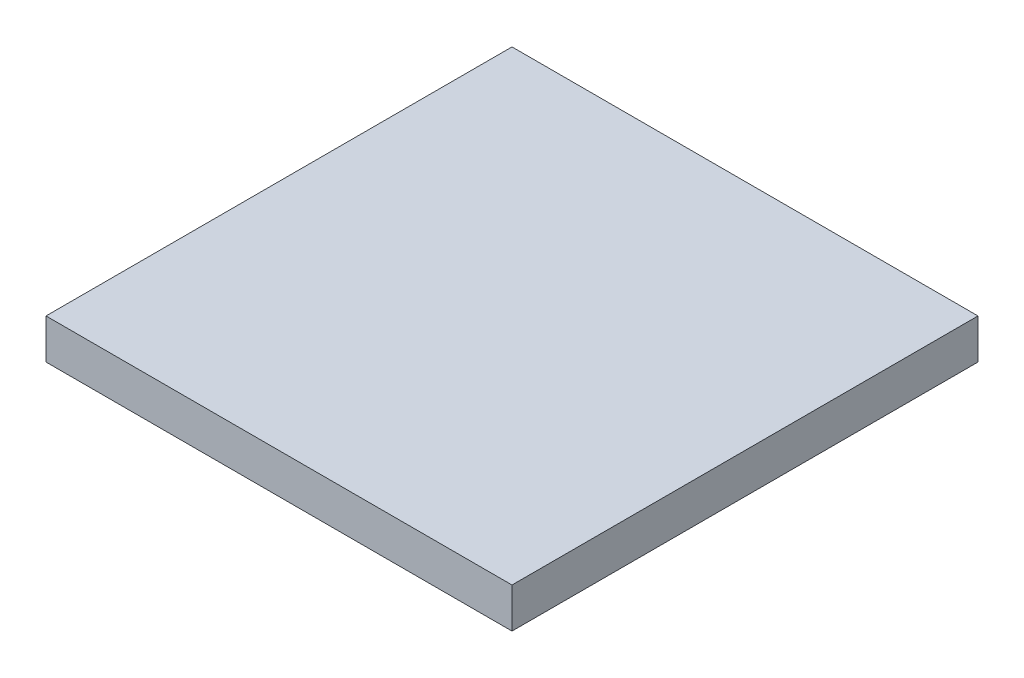
SolidWorks part; units mm, degrees
ref_plane "Front Plane" through (0, 0, 0) normal (0, 0, 1) x (1, 0, 0)
ref_plane "Top Plane" through (0, 0, 0) normal (0, 1, 0) x (1, 0, 0)
ref_plane "Right Plane" through (0, 0, 0) normal (1, 0, 0) x (0, 0, -1)
sketch "Sketch1" plane through (0, 0, 0) normal (0, 1, 0) x (1, 0, 0)
  line L1 (-35, -35) -> (35, -35)
  line L2 (-35, -35) -> (-35, 35)
  line L3 (-35, 35) -> (35, 35)
  line L4 (35, -35) -> (35, 35)
  line L5 (-35, -35) -> (35, 35) construction
  line L6 (-35, 35) -> (35, -35) construction
  point P1 (0, 0)
  dimension "D1" = 70
  dimension "D2" = 70
extrude "Boss-Extrude1" add sketch "Sketch1" along normal blind 6
